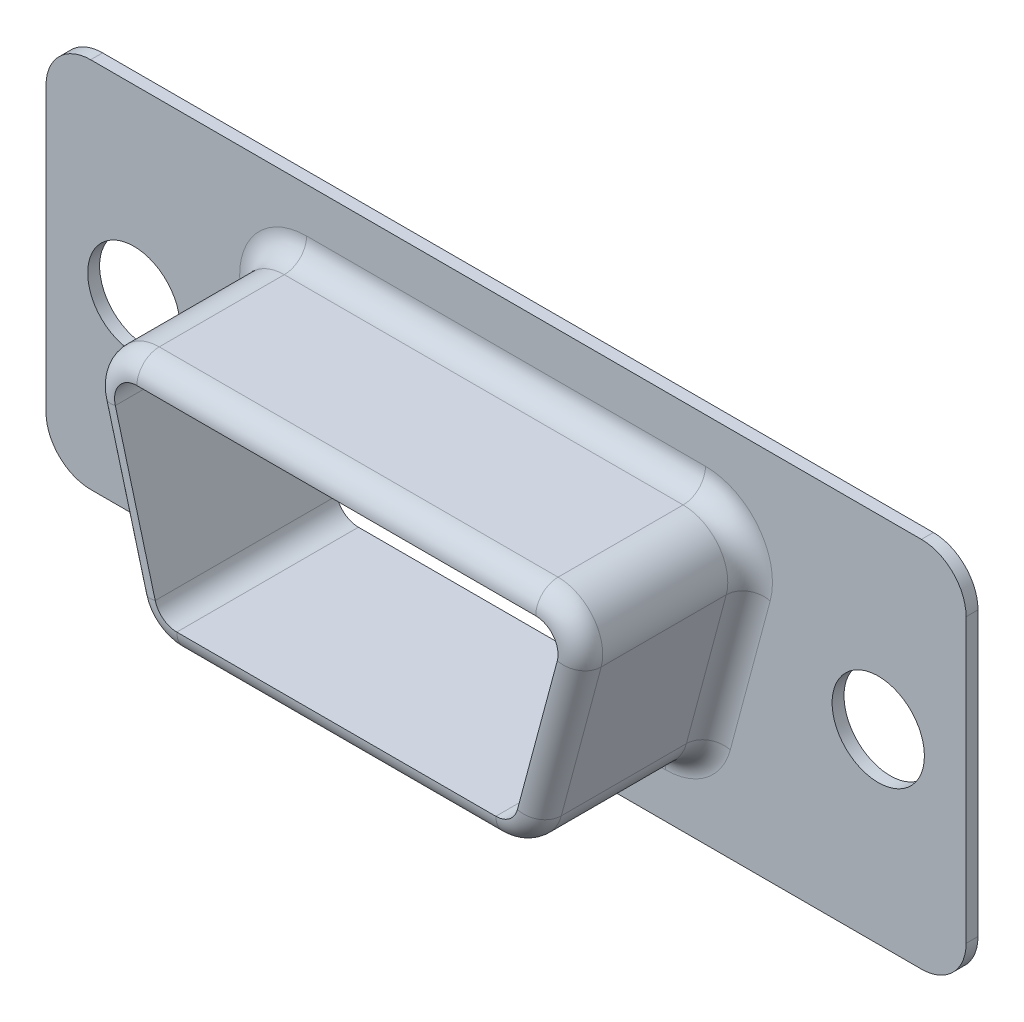
SolidWorks part; units mm, degrees
ref_plane "Front Plane" through (0, 0, 0) normal (0, 0, 1) x (1, 0, 0)
ref_plane "Top Plane" through (0, 0, 0) normal (0, 1, 0) x (1, 0, 0)
ref_plane "Right Plane" through (0, 0, 0) normal (1, 0, 0) x (0, 0, -1)
sketch "Sketch1" plane through (0, 0, 0) normal (0, 0, 1) x (1, 0, 0)
  line L0 (-135.2667, 0) -> (178.1738, 0) construction
  line L1 (0, 93.814) -> (0, -102.1772) construction
  line L2 (-8.146, 2.1118) -> (-6.8062, -2.8882) construction
  line L3 (-13.95, 6.25) -> (13.95, 6.25)
  line L4 (-15.45, 4.75) -> (-15.45, -4.75)
  line L5 (-13.95, -6.25) -> (13.95, -6.25)
  line L6 (15.45, 4.75) -> (15.45, -4.75)
  line L7 (-15.45, 6.25) -> (15.45, -6.25) construction
  line L8 (-15.45, -6.25) -> (15.45, 6.25) construction
  line L9 (-6.6971, 4) -> (6.6971, 4) construction
  line L10 (8.146, 2.1118) -> (6.8062, -2.8882) construction
  line L11 (-5.3573, -4) -> (5.3573, -4) construction
  line L12 (-6.6971, 3.25) -> (6.6971, 3.25)
  line L13 (-8.25, 4) -> (8.25, -4) construction
  line L14 (-8.25, -4) -> (8.25, 4) construction
  line L15 (7.4215, 2.3059) -> (6.0818, -2.6941)
  line L16 (-5.3573, -3.25) -> (5.3573, -3.25)
  line L17 (-7.4215, 2.3059) -> (-6.0818, -2.6941)
  circle A0 centre (-12.5, 0) radius 1.55
  circle A1 centre (12.5, 0) radius 1.55
  arc A2 (8.146, 2.1118) -> (6.6971, 4) centre (6.6971, 2.5) ccw construction
  arc A3 (-8.146, 2.1118) -> (-6.6971, 4) centre (-6.6971, 2.5) cw construction
  arc A4 (5.3573, -4) -> (6.8062, -2.8882) centre (5.3573, -2.5) ccw construction
  arc A5 (-6.8062, -2.8882) -> (-5.3573, -4) centre (-5.3573, -2.5) ccw construction
  arc A6 (13.95, 6.25) -> (15.45, 4.75) centre (13.95, 4.75) cw
  arc A7 (13.95, -6.25) -> (15.45, -4.75) centre (13.95, -4.75) ccw
  arc A8 (-15.45, -4.75) -> (-13.95, -6.25) centre (-13.95, -4.75) ccw
  arc A9 (-13.95, 6.25) -> (-15.45, 4.75) centre (-13.95, 4.75) ccw
  arc A10 (7.4215, 2.3059) -> (6.6971, 3.25) centre (6.6971, 2.5) ccw
  arc A11 (5.3573, -3.25) -> (6.0818, -2.6941) centre (5.3573, -2.5) ccw
  arc A12 (-6.0818, -2.6941) -> (-5.3573, -3.25) centre (-5.3573, -2.5) ccw
  arc A13 (-7.4215, 2.3059) -> (-6.6971, 3.25) centre (-6.6971, 2.5) cw
  point P5 (0, 0)
  point P14 (0, 0)
  dimension "D1" = 16.5
  dimension "D6" = 1.5
  dimension "D7" = 1.5
  dimension "D2" = 1.5
  dimension "D8" = 3.1
  dimension "D3" = 30.9
  dimension "D4" = 12.5
  dimension "D5" = 12.5
  dimension "D9" = 0.75
extrude "Boss-Extrude1" add sketch "Sketch1" along normal blind 0.4 contours L3 A9 L4 A8 L5 A7 L6 A6 A1 A0 A5 L2 A3 L9 A2 L10 A4 L11 region at (0, 5.9167, 0)
sketch "Sketch2" plane through (0, 0, 0.4) normal (0, 0, 1) x (1, 0, 0)
  line L0 (-7.4215, 2.3059) -> (-6.0818, -2.6941)
  line L1 (-5.3573, -3.25) -> (5.3573, -3.25)
  line L2 (6.0818, -2.6941) -> (7.4215, 2.3059)
  line L3 (6.6971, 3.25) -> (-6.6971, 3.25)
  line L25 (6.6971, 4) -> (-6.6971, 4)
  line L26 (6.8062, -2.8882) -> (8.146, 2.1118)
  line L27 (-5.3573, -4) -> (5.3573, -4)
  line L28 (-8.146, 2.1118) -> (-6.8062, -2.8882)
  arc A0 (-6.0818, -2.6941) -> (-5.3573, -3.25) centre (-5.3573, -2.5) ccw
  arc A1 (5.3573, -3.25) -> (6.0818, -2.6941) centre (5.3573, -2.5) ccw
  arc A2 (7.4215, 2.3059) -> (6.6971, 3.25) centre (6.6971, 2.5) ccw
  arc A3 (-6.6971, 3.25) -> (-7.4215, 2.3059) centre (-6.6971, 2.5) ccw
  arc A24 (-6.6971, 4) -> (-8.146, 2.1118) centre (-6.6971, 2.5) ccw
  arc A25 (8.146, 2.1118) -> (6.6971, 4) centre (6.6971, 2.5) ccw
  arc A26 (5.3573, -4) -> (6.8062, -2.8882) centre (5.3573, -2.5) ccw
  arc A27 (-6.8062, -2.8882) -> (-5.3573, -4) centre (-5.3573, -2.5) ccw
  dimension "D1" = 0.75
extrude "Boss-Extrude2" add sketch "Sketch2" along normal blind 5.7
fillet "Fillet1" radius 0.75 16 edges at (-7.8871, 3.4131, 0.4) (0, 4, 0.4) (7.8871, 3.4131, 0.4) (7.4761, -0.3882, 0.4) (6.2705, -3.69, 0.4) (0, -4, 0.4) (-6.2705, -3.69, 0.4) (-7.8871, 3.4131, 6.1) (0, 4, 6.1) (7.8871, 3.4131, 6.1) (7.4761, -0.3882, 6.1) (6.2705, -3.69, 6.1) (0, -4, 6.1) (-6.2705, -3.69, 6.1) (-7.4761, -0.3882, 0.4) (-7.4761, -0.3882, 6.1)
